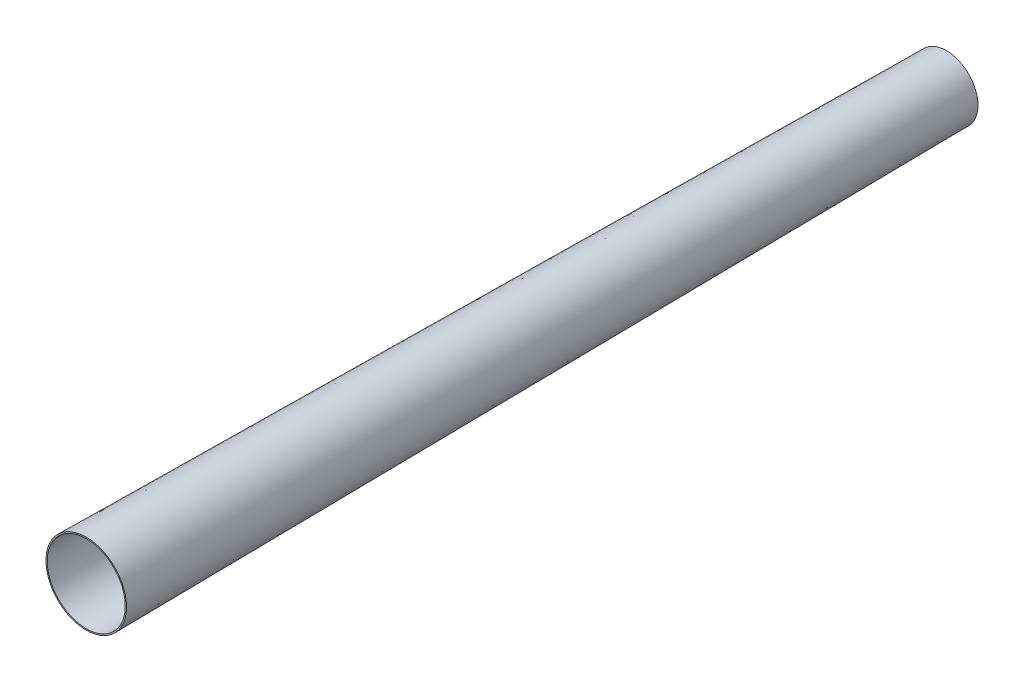
SolidWorks part; units mm, degrees
ref_plane "Front Plane" through (0, 0, 0) normal (0, 0, 1) x (1, 0, 0)
ref_plane "Top Plane" through (0, 0, 0) normal (0, 1, 0) x (1, 0, 0)
ref_plane "Right Plane" through (0, 0, 0) normal (1, 0, 0) x (0, 0, -1)
sketch "Sketch1" plane through (0, 0, 0) normal (0, 0, 1) x (1, 0, 0)
  circle A0 centre (0, 0) radius 11.9044
  circle A1 centre (0, 0) radius 12.4044
  dimension "D2" = 24.8088
  dimension "D1" = 0.5
ref_plane "Plane1" through (0, 0, 337.5026) normal (0, 0, 1) x (1, 0, 0)
sketch "Sketch2" plane through (0, 0, 337.5026) normal (0, 0, 1) x (1, 0, 0)
  circle A0 centre (0, 0) radius 15.8156
  circle A1 centre (0, 0) radius 15.3156
  dimension "D2" = 31.6312
  dimension "D1" = 0.5
loft "Loft1" add section "Sketch1" section "Sketch2" start constraint default connector at (-11.2205, -5.2886, 0) connector at (-14.3273, -6.698, 337.5026)
shell "Shell1" thickness 0.5 removed face at (12.4044, 0, 0) removed face at (15.8156, 0, 337.5026)
